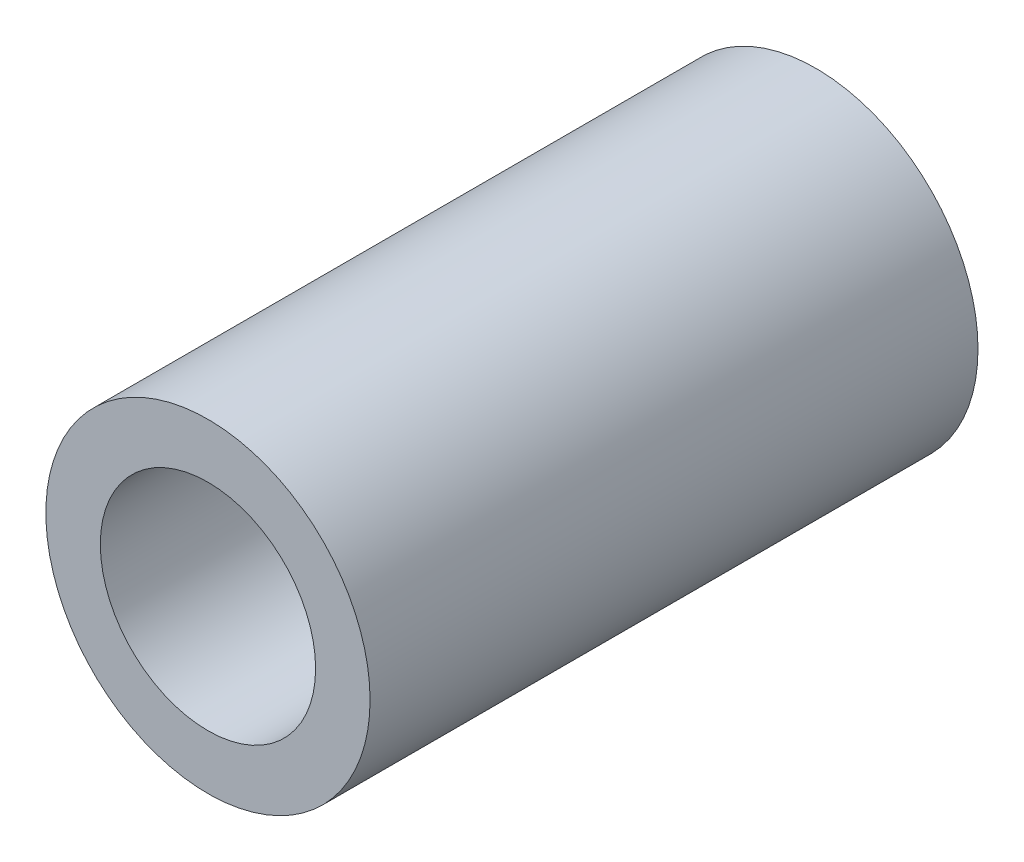
SolidWorks part; units mm, degrees
ref_plane "Front Plane" through (0, 0, 0) normal (0, 0, 1) x (1, 0, 0)
ref_plane "Top Plane" through (0, 0, 0) normal (0, 1, 0) x (1, 0, 0)
ref_plane "Right Plane" through (0, 0, 0) normal (1, 0, 0) x (0, 0, -1)
sketch "Sketch1" plane through (0, 0, 0) normal (0, 0, 1) x (1, 0, 0)
  circle A0 centre (0, 0) radius 3.175
  circle A1 centre (0, 0) radius 2.1082
  dimension "OD" = 6.35
  dimension "ID" = 4.2164
extrude "Extrude1" add sketch "Sketch1" along normal mid plane 11.9062
sketch "Sketch2" plane through (0, 0, 0) normal (1, 0, 0) x (0, 0, -1)
  line L0 (-5.9531, -2.1082) -> (5.9531, -2.1082) construction
  line L3 (5.9531, 2.1082) -> (-5.9531, 2.1082) construction
  line L5 (-5.9531, -2.1082) -> (5.9531, -2.1082)
  line L6 (5.9531, 2.1082) -> (-5.9531, 2.1082)
sketch "Sketch4" plane through (0, 0, 5.9531) normal (0, 0, 1) x (1, 0, 0)
  line L0 (0, 0) -> (-1.4907, 1.4907)
  line L1 (0, -1.7463) -> (0, 1.7463) construction
  circle A0 centre (0, 0) radius 2.1082 construction
  dimension "D1" = 45
